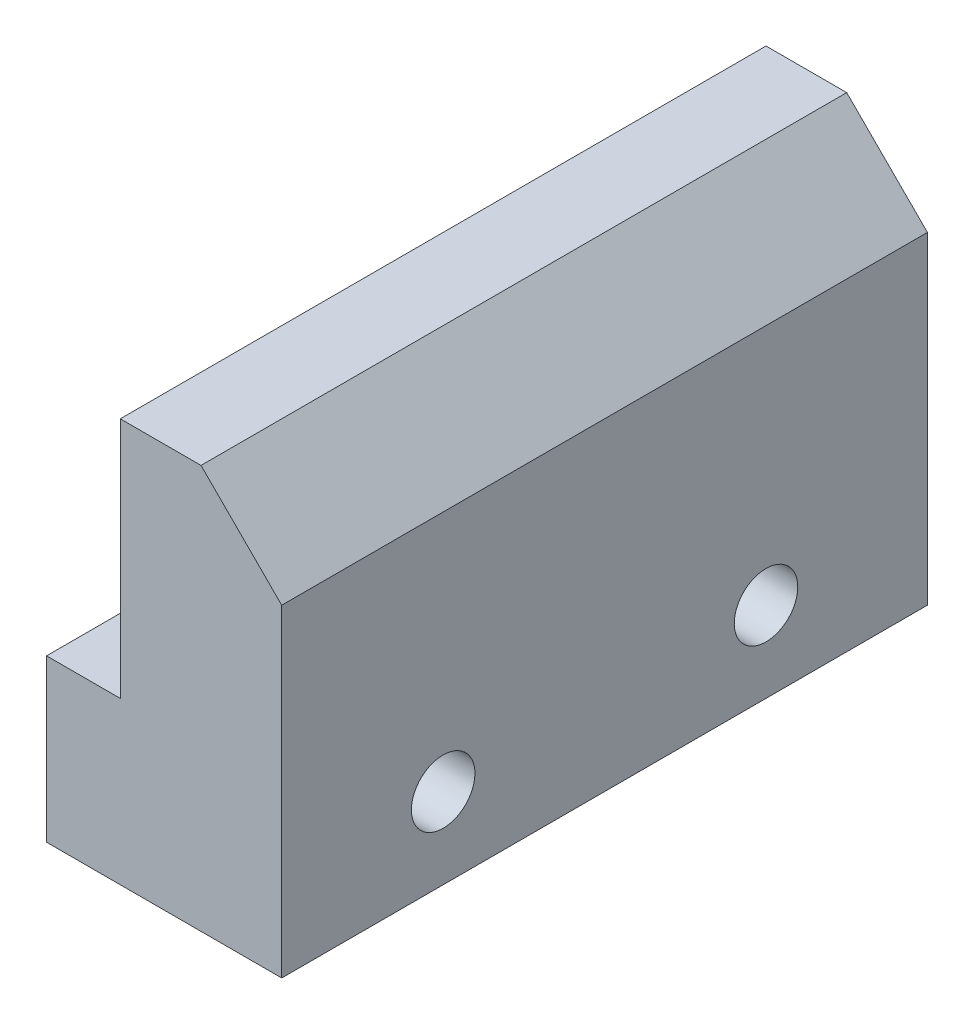
SolidWorks part; units mm, degrees
material "PETG"
ref_plane "Front Plane" through (0, 0, 0) normal (0, 0, 1) x (1, 0, 0)
ref_plane "Top Plane" through (0, 0, 0) normal (0, 1, 0) x (1, 0, 0)
ref_plane "Right Plane" through (0, 0, 0) normal (1, 0, 0) x (0, 0, -1)
sketch "Sketch1" plane through (0, 0, 0) normal (0, 0, 1) x (1, 0, 0)
  line L0 (11.6, 63.5) -> (37, 38.1)
  line L1 (0, -12.7) -> (37, -12.7)
  line L2 (0, -12.7) -> (0, 12.7)
  line L3 (0, 12.7) -> (11.6, 12.7)
  line L6 (11.6, 63.5) -> (11.6, 12.7)
  line L8 (37, 38.1) -> (37, -12.7)
  line L9 (11.6, 50.8) -> (24.3, 50.8)
  dimension "D1" = 25.4
  dimension "D2" = 37
  dimension "D3" = 50.8
  dimension "D4" = 25.4
  dimension "D5" = 25.4
extrude "Boss-Extrude1" add sketch "Sketch1" along normal mid plane 101.6 contours L9 L6 L3 L2 L1 L8 L0 region at (20.9426, 14.763, 0)
sketch "Sketch2" plane through (37, 0, 0) normal (1, 0, 0) x (0, 0, -1)
  line L0 (-25.4, 0) -> (0, 0) construction
  line L1 (0, 0) -> (25.4, 0) construction
  line L2 (-50.8, 38.1) -> (-50.8, -12.7) construction
  circle A0 centre (-25.4, 0) radius 2.8
  circle A1 centre (25.4, 0) radius 2.8
  dimension "D1" = 25.4
  dimension "D2" = 5.6
extrude "Cut-Extrude1" cut sketch "Sketch2" against normal through all
sketch "Sketch3" plane through (37, 0, 0) normal (1, 0, 0) x (0, 0, -1)
  circle A0 centre (-25.4, 0) radius 5
  circle A1 centre (25.4, 0) radius 5
  dimension "D1" = 10
extrude "Cut-Extrude2" cut sketch "Sketch3" against normal offset from surface (27 mm away) 10 up to face at (0, 2.8, 25.4)
equation "\"D2@Sketch1\"=37mm"
